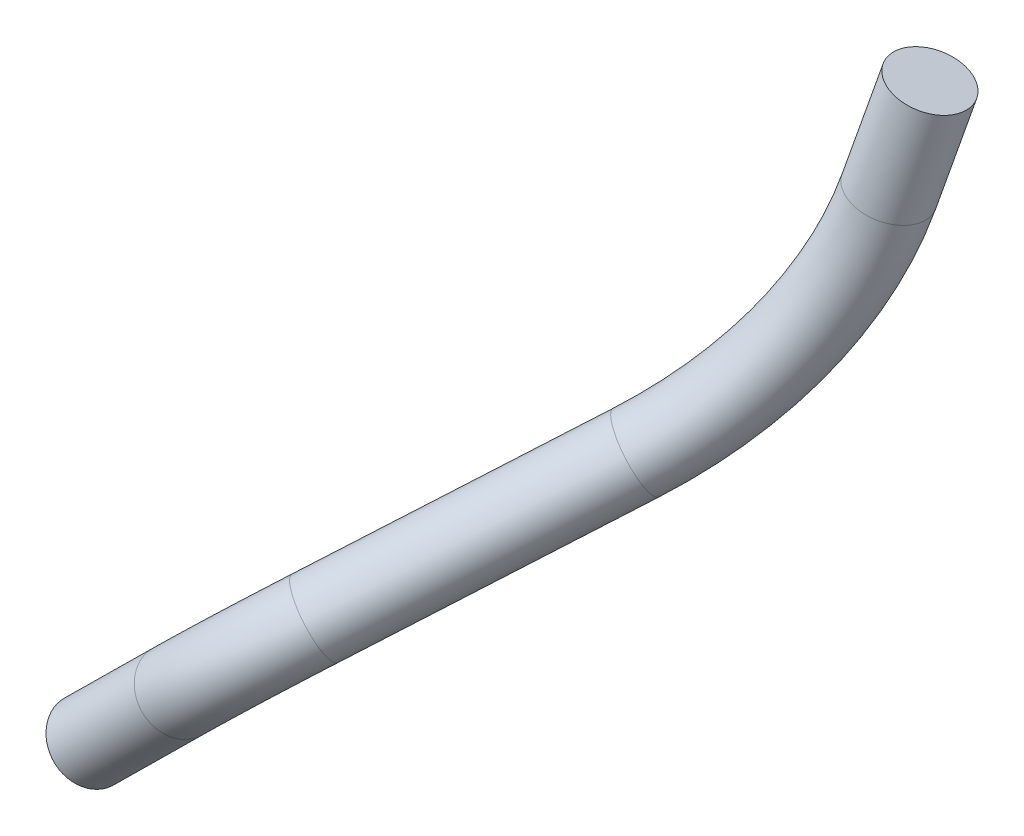
SolidWorks part; units mm, degrees
ref_plane "X-Y Datum" through (0, 0, 0) normal (0, 0, 1) x (1, 0, 0)
ref_plane "X-Z Datum" through (0, 0, 0) normal (0, 1, 0) x (1, 0, 0)
ref_plane "Y-Z Datum" through (0, 0, 0) normal (1, 0, 0) x (0, 0, -1)
sketch3d "3DSketch1"
  line L0 (249.9103, 151.4778, 165.0533) -> (253.6203, 165.14, 163.3218)
  line L1 (200.591, 91.8187, 210.3483) -> (188.8507, 80.2108, 210.3483)
  line L2 (212.6835, 103.2218, 204.1716) -> (232.5301, 120.7986, 181.3218)
  line L3 (195.6578, 87.5142, 210.3483) -> (196.2341, 86.9379, 210.3483) construction
  line L4 (214.5506, 105.7551, 201.8304) -> (214.8834, 104.2903, 201.8304) construction
  arc A1 (253.6579, 165.1264, 159.3218) -> (253.6579, 165.1264, 167.3218) centre (253.6579, 165.1264, 163.3218) ccw construction
  arc A2 (253.6203, 165.14, 168.0218) -> (253.6203, 165.14, 158.6218) centre (253.6203, 165.14, 163.3218) ccw construction
  arc A3 (232.5301, 120.7986, 181.3218) -> (249.9103, 151.4778, 165.0533) centre (222.3711, 164.1234, 205.8249) ccw
  arc A4 (212.6835, 103.2218, 204.1716) -> (200.591, 91.8187, 210.3483) centre (201.7257, 90.6711, 184.9996) ccw
  point P0 (198.0165, 89.2733, 210.3483)
  point P1 (253.6579, 165.1264, 163.3218)
  point P5 (207.3187, 98.4705, 210.3483)
  point P9 (252.2924, 161.3666, 163.3218)
  point P17 (252.0158, 160.7224, 163.3218)
  point P18 (244.4448, 131.3507, 167.6042)
  point P19 (262.9619, 156.8612, 235.4945)
  point P21 (195.9459, 87.226, 210.3483)
  point P22 (219.548, 72.6454, 186.6135)
  point P25 (195.9459, 87.226, 210.3483)
  point P29 (214.717, 105.0227, 201.8304)
  point P40 (214.717, 105.0227, 201.8304)
  dimension "D1" = 50.8
  dimension "D2" = 25.4
  dimension "D3" = 16.51
sweep "Sweep1" add path "3DSketch1" circular profile diameter 9.398 parameters "D3"=9.398
